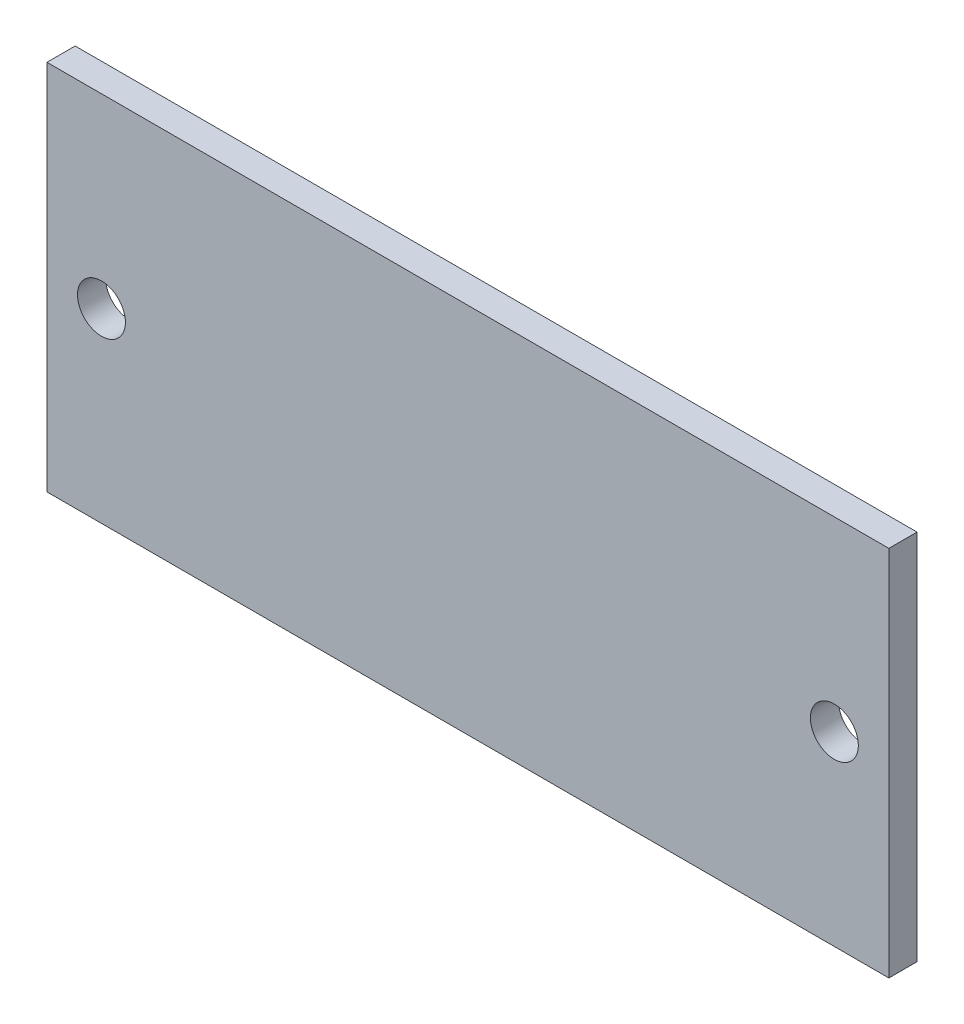
SolidWorks part; units mm, degrees
ref_plane "Front Plane" through (0, 0, 0) normal (0, 0, 1) x (1, 0, 0)
ref_plane "Top Plane" through (0, 0, 0) normal (0, 1, 0) x (1, 0, 0)
ref_plane "Right Plane" through (0, 0, 0) normal (1, 0, 0) x (0, 0, -1)
sketch "Sketch2" plane through (0, 0, 0) normal (0, 0, 1) x (1, 0, 0)
  line L1 (-22.4, 9.9) -> (22.4, 9.9)
  line L2 (-22.4, 9.9) -> (-22.4, -9.9)
  line L3 (-22.4, -9.9) -> (22.4, -9.9)
  line L4 (22.4, 9.9) -> (22.4, -9.9)
  line L5 (-22.4, 9.9) -> (22.4, -9.9) construction
  line L6 (-22.4, -9.9) -> (22.4, 9.9) construction
  point P0 (0, 0)
  dimension "D1" = 19.8
  dimension "D2" = 44.8
extrude "Boss-Extrude1" add sketch "Sketch2" along normal blind 1.5
sketch "Sketch3" plane through (0, 0, 1.5) normal (0, 0, 1) x (1, 0, 0)
  circle A0 centre (-19.5, 0) radius 1.275
  point P2 (0, 0)
  dimension "D1" = 2.55
  dimension "D2" = 19.5
extrude "Cut-Extrude1" cut sketch "Sketch3" against normal through all
mirror "Mirror1" about plane through (0, 0, 0) normal (1, 0, 0) of "Cut-Extrude1"
